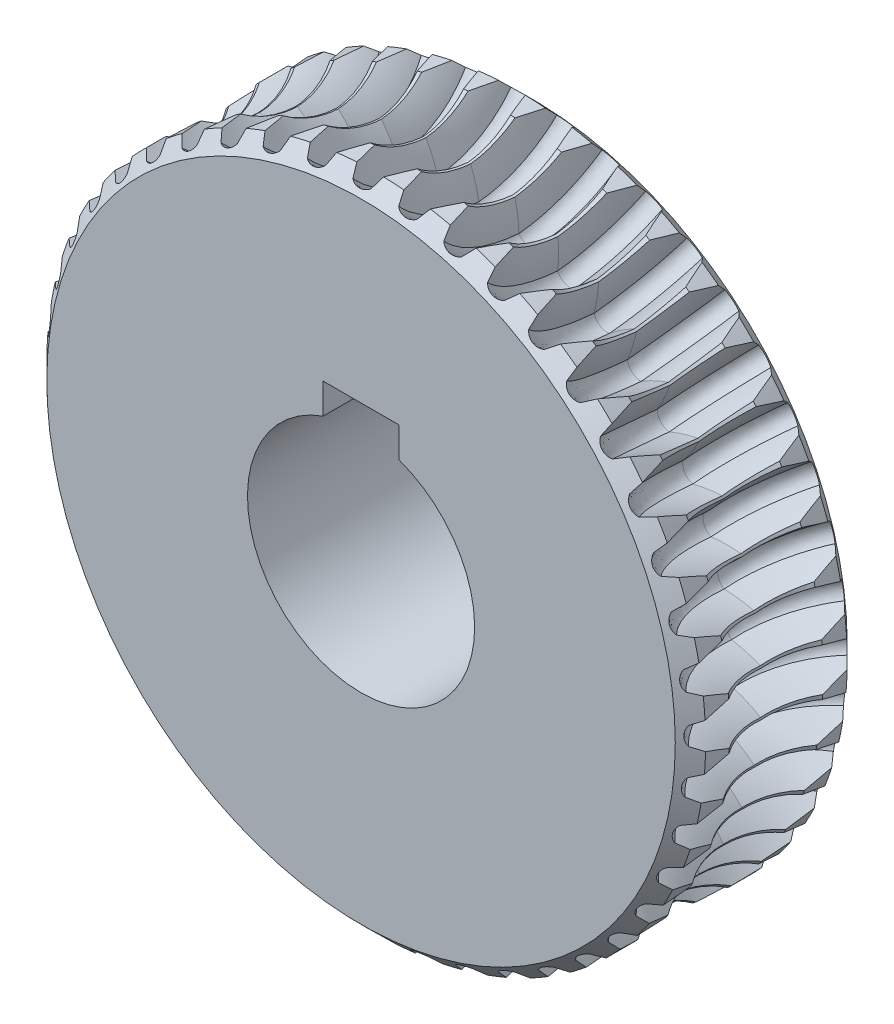
SolidWorks part; units mm, degrees
ref_plane "Front Plane" through (0, 0, 0) normal (0, 0, 1) x (1, 0, 0)
ref_plane "Top Plane" through (0, 0, 0) normal (0, 1, 0) x (1, 0, 0)
ref_plane "Right Plane" through (0, 0, 0) normal (1, 0, 0) x (0, 0, -1)
sketch "Sketch1" plane through (0, 0, 0) normal (0, 0, 1) x (1, 0, 0)
  line L1 (-5, 18.1421) -> (5, 18.1421)
  line L2 (-5, 18.1421) -> (-5, 14.1421)
  line L4 (5, 18.1421) -> (5, 14.1421)
  arc A0 (-5, 14.1421) -> (5, 14.1421) centre (0, 0) ccw
  circle A1 centre (0, 0) radius 43.5
  point P10 (0, 18.1421)
  dimension "D1" = 87
  dimension "D2" = 30
  dimension "D3" = 10
  dimension "D4" = 4
extrude "Boss-Extrude1" add sketch "Sketch1" along normal mid plane 22.7
chamfer "Chamfer1" distance 2 angle 45 2 edges at (43.5, 0, 11.35) (43.5, 0, -11.35)
sketch "Sketch2" plane through (0, 0, 0) normal (1, 0, 0) x (0, 0, -1)
  line L0 (-11.35, 0) -> (11.35, 0) construction
  line L1 (-11.35, 41.5) -> (-11.35, -41.5) construction
  circle A0 centre (0, -52) radius 10.5
  point P5 (-11.35, 0)
  dimension "D2" = 21
  dimension "D1" = 52
revolve "Cut-Revolve1" cut sketch "Sketch2" angle 360 about L0
sketch "Sketch3" plane through (0, 0, 0) normal (1, 0, 0) x (0, 0, -1)
  circle A1 centre (0, -52) radius 10.5
  circle A2 centre (0, -52) radius 10.5
  dimension "D1" = 0
curve "Helix/Spiral1" pitch 6 height 1.5 turns 0.25
sketch "Sketch4" plane through (0, 0, 0) normal (0, 0, 1) x (1, 0, 0)
  line L0 (0, 0) -> (0, -43.5) construction
  line L1 (3.45, -44.44) -> (-3.45, -44.44)
  line L2 (-3.45, -44.44) -> (-3.45, -42.44)
  line L3 (3.45, -44.44) -> (3.45, -42.44)
  circle A0 centre (0, 0) radius 43.5 construction
  arc A1 (-1.2018, -37.79) -> (1.2018, -37.79) centre (0, -39.13) cw
  arc A2 (-3.45, -42.44) -> (-1.2018, -37.79) centre (-18.3636, -32.3611) ccw
  arc A3 (3.45, -42.44) -> (1.2018, -37.79) centre (18.3636, -32.3611) cw
  point P9 (-3.45, -42.5139)
  point P16 (0, -44.44)
  point P17 (-3.45, -42.2388)
  point P18 (3.45, -44.5722)
  dimension "D2" = 1.8
  dimension "D4" = 18
  dimension "D1" = 39.13
  dimension "D3" = 6.9
  dimension "D5" = 4.65
  dimension "D6" = 1.34
  dimension "D7" = 2
sweep "Cut-Sweep1" cut profiles "Sketch4" path "Helix/Spiral1"
mirror "Mirror1" about plane through (0, 0, 0) normal (0, 0, 1) of "Cut-Sweep1"
pattern_circular "CirPattern1" count 44 over 360 about axis through (0, 0, 11.35) along (0, 0, 1) of "Cut-Sweep1", "Mirror1"
